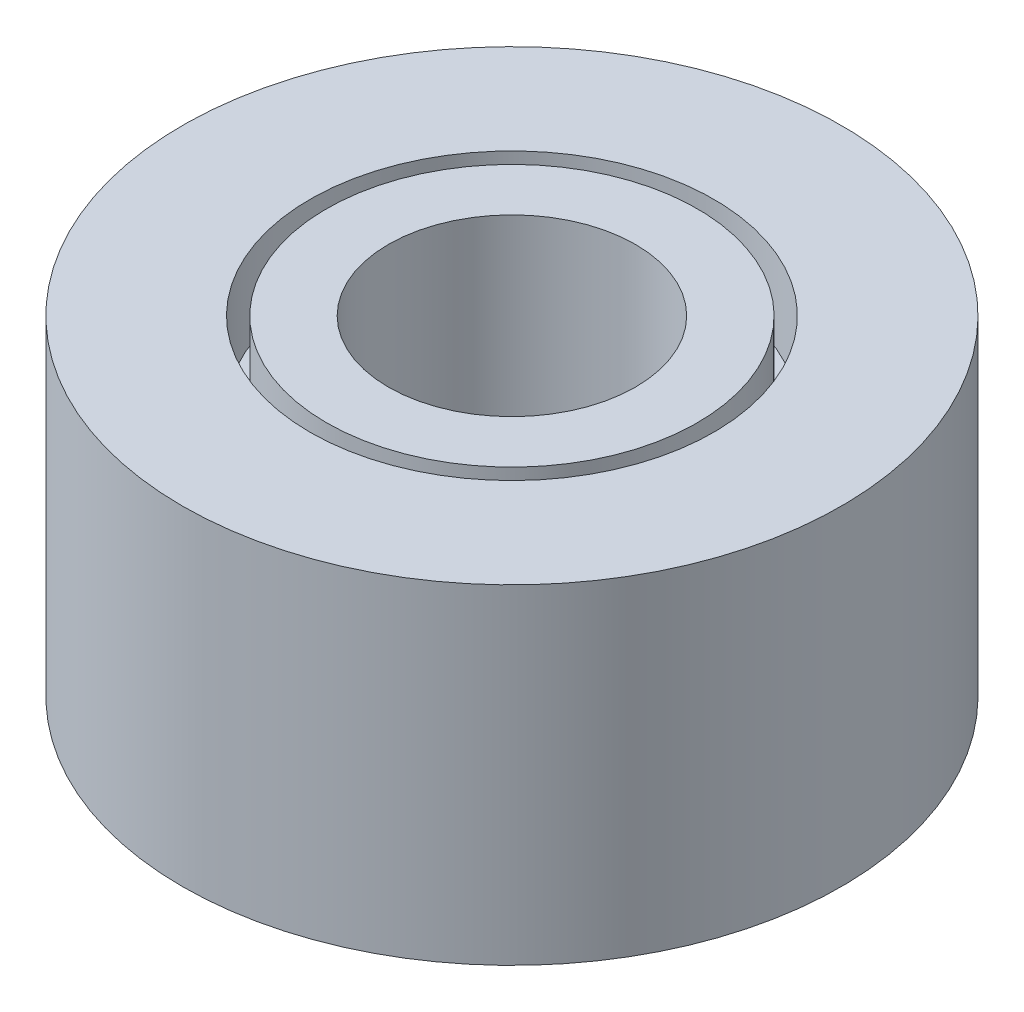
SolidWorks part; units mm, degrees
ref_plane "前视基准面" through (0, 0, 0) normal (0, 0, 1) x (1, 0, 0)
ref_plane "上视基准面" through (0, 0, 0) normal (0, 1, 0) x (1, 0, 0)
ref_plane "右视基准面" through (0, 0, 0) normal (1, 0, 0) x (0, 0, -1)
other "Configuration Table"
sketch "草图1" plane through (0, 0, 0) normal (0, 1, 0) x (1, 0, 0)
  circle A0 centre (0, 0) radius 4
  circle A1 centre (0, 0) radius 1.5
  circle A2 centre (0, 0) radius 2.25
  dimension "D1" = 3
  dimension "D2" = 8
  dimension "D3" = 4.5
extrude "凸台-拉伸1" add sketch "草图1" along normal blind 4 contours A1 | A0 region at (0, 0, 0)
extrude "切除-拉伸-薄壁1" cut sketch "草图1<3>" along normal blind 1 thin contours A2 thin type one direction wall 0.2
sketch "草图1<3>" plane through (0, 0, 0) normal (0, 1, 0) x (1, 0, 0) same geometry as "草图1"
extrude "切除-拉伸-薄壁2" cut sketch "草图1<4>" against normal blind 1 from surface thin contours A2 starting at face at (0, 4, 4) thin type one direction wall 0.2
sketch "草图1<4>" plane through (0, 0, 0) normal (0, 1, 0) x (1, 0, 0) same geometry as "草图1"
